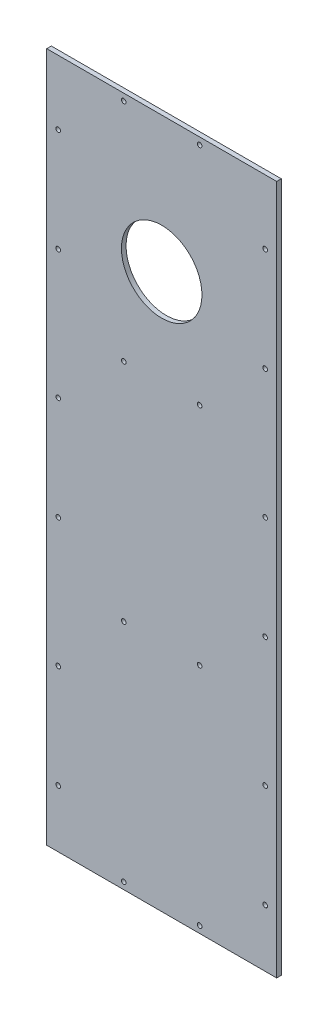
SolidWorks part; units mm, degrees
material "Alumina"
ref_plane "Front Plane" through (0, 0, 0) normal (0, 0, 1) x (1, 0, 0)
ref_plane "Top Plane" through (0, 0, 0) normal (0, 1, 0) x (1, 0, 0)
ref_plane "Right Plane" through (0, 0, 0) normal (1, 0, 0) x (0, 0, -1)
sketch "Sketch1" plane through (0, 0, 0) normal (0, 0, 1) x (1, 0, 0)
  line L1 (50, -150) -> (-50, -150)
  line L2 (50, -150) -> (50, 150)
  line L3 (50, 150) -> (-50, 150)
  line L4 (-50, -150) -> (-50, 150)
  line L5 (50, -150) -> (-50, 150) construction
  line L6 (50, 150) -> (-50, -150) construction
  point P0 (0, 0)
  dimension "D1" = 100
  dimension "D2" = 300
extrude "Boss-Extrude1" add sketch "Sketch1" along normal blind 2
sketch "Sketch2" plane through (0, 0, 2) normal (0, 0, 1) x (1, 0, 0)
  line L0 (-50, 150) -> (-50, -150) construction
  line L1 (50, 150) -> (-50, 150) construction
  line L2 (-50, -150) -> (50, -150) construction
  line L4 (0, -1.1) -> (0, 1.1) construction
  line L5 (-45, 122) -> (-45, 21) construction
  circle A0 centre (-45, 122) radius 1
  circle A1 centre (-45, 77) radius 1
  circle A2 centre (45, 122) radius 1
  circle A3 centre (45, 77) radius 1
  circle A4 centre (-45, 21) radius 1
  circle A5 centre (-45, -24) radius 1
  circle A6 centre (45, 21) radius 1
  circle A7 centre (45, -24) radius 1
  circle A8 centre (-45, -80) radius 1
  circle A9 centre (-45, -125) radius 1
  circle A10 centre (45, -80) radius 1
  circle A11 centre (45, -125) radius 1
  circle A13 centre (16.5, -147) radius 1
  circle A14 centre (-16.5, -147) radius 1
  circle A15 centre (-16.5, -49) radius 1
  circle A16 centre (16.5, -49) radius 1
  circle A17 centre (-16.5, 49) radius 1
  circle A18 centre (16.5, 49) radius 1
  circle A19 centre (-16.5, 147) radius 1
  circle A20 centre (16.5, 147) radius 1
  dimension "D1" = 2
  dimension "D3" = 28
  dimension "D4" = 2
  dimension "D6" = 5
  dimension "D10" = 2
  dimension "D11" = 33
  dimension "D13" = 3
  dimension "D14" = 90
  dimension "D15" = 5
  dimension "D16" = 3
  dimension "D2" = 5
  dimension "D9" = 25
  dimension "D17" = 101
  dimension "D7" = 2
  dimension "D8" = 3
  dimension "D12" = 4
extrude "Cut-Extrude1" cut sketch "Sketch2" against normal blind 10
sketch "Sketch3" plane through (0, 0, 0) normal (0, 0, -1) x (-1, 0, 0)
  line L0 (-50, 150) -> (50, 150) construction
  line L1 (-50, -150) -> (-50, 150) construction
  circle A0 centre (0, 91) radius 17.5
  dimension "D2" = 35
  dimension "D3" = 50
  dimension "D1" = 59
extrude "Cut-Extrude2" cut sketch "Sketch3" against normal blind 10
